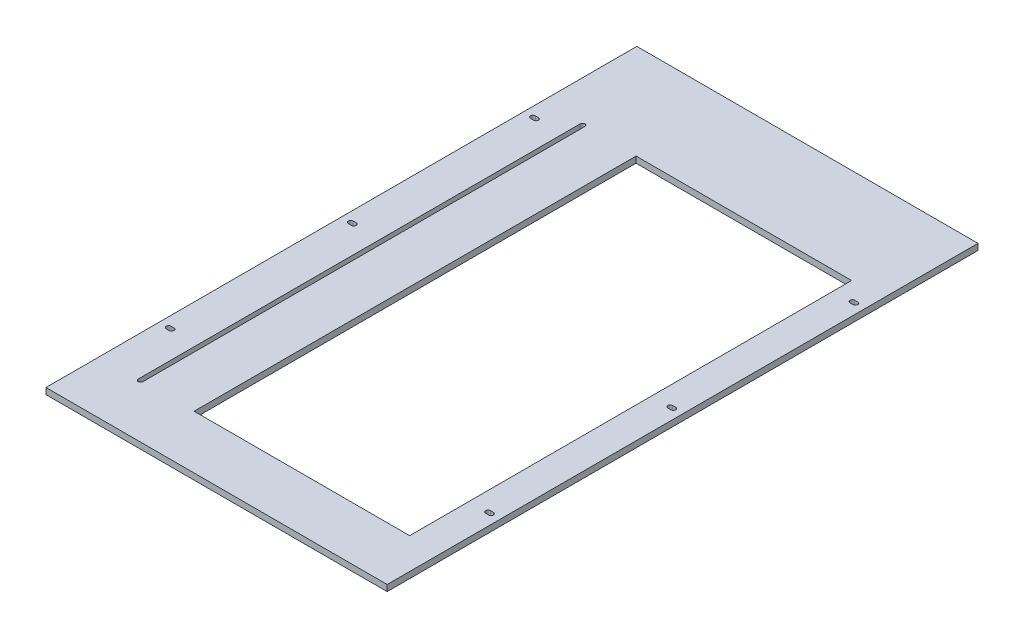
SolidWorks part; units mm, degrees
ref_plane "前基準面" through (0, 0, 0) normal (0, 0, 1) x (1, 0, 0)
ref_plane "上基準面" through (0, 0, 0) normal (0, 1, 0) x (1, 0, 0)
ref_plane "右基準面" through (0, 0, 0) normal (1, 0, 0) x (0, 0, -1)
sketch "草圖1" plane through (0, 0, 0) normal (0, 1, 0) x (1, 0, 0)
  line L0 (0, 0) -> (326.8973, 0) construction
  line L1 (0, 0) -> (0, 183.7767) construction
  line L3 (-113.7553, 194.0216) -> (106.2447, 194.0216)
  line L4 (-113.7553, 194.0216) -> (-113.7553, -186.9784)
  line L5 (-113.7553, -186.9784) -> (106.2447, -186.9784)
  line L6 (106.2447, 194.0216) -> (106.2447, -186.9784)
  dimension "D1" = 381
  dimension "D2" = 220
extrude "填料-伸長1" add sketch "草圖1" against normal blind 4
sketch "草圖2" plane through (0, 0, 0) normal (0, 1, 0) x (1, 0, 0)
  line L0 (-113.7553, 194.0216) -> (-113.7553, -186.9784) construction
  line L1 (-113.7553, -186.9784) -> (106.2447, -186.9784) construction
  line L2 (-106.7553, -113.9784) -> (99.2447, -113.9784) construction
  line L3 (-106.7553, -113.9784) -> (-106.7553, 3.5216) construction
  point P0 (-106.7553, -113.9784)
  point P6 (99.2447, -113.9784)
  point P8 (99.2447, 3.5216)
  point P9 (99.2447, 121.0216)
  point P10 (-106.7553, 3.5216)
  point P11 (-106.7553, 121.0216)
  dimension "D1" = 7
  dimension "D2" = 73
  dimension "D5" = 206
  dimension "D6" = 117.5
  dimension "D3" = 2
  dimension "D4" = 3
hole_wizard "Ø2.9 (2.9) 直徑孔1" positions "3D草圖4" profile "草圖5" hole size "Ø2.9" standard "GB" end condition through all
sketch3d "3D草圖4"
  point P0 (-106.7553, 0, -121.0216)
  point P3 (-106.7553, 0, -3.5216)
  point P6 (-106.7553, 0, 113.9784)
  point P9 (99.2447, 0, 113.9784)
  point P12 (99.2447, 0, -3.5216)
  point P15 (99.2447, 0, -121.0216)
sketch "草圖5" plane through (-106.7553, 0, -121.0216) normal (1, 0, 0) x (0, 0, 1)
  line L0 (0, 0) -> (0, 4)
  line L1 (0, 4) -> (1.45, 4)
  line L2 (1.45, 4) -> (1.45, 0)
  line L5 (1.45, 0) -> (0, 0)
  line L11 (0, -6.35) -> (0, 107.95) construction
  dimension "貫穿孔直徑" = 2.9
  dimension "貫穿孔深度" = 4
sketch "草圖6" plane through (0, 0, 0) normal (0, 1, 0) x (1, 0, 0)
  line L0 (-113.7553, -186.9784) -> (106.2447, -186.9784) construction
  line L1 (-52.7553, 132.5216) -> (86.2447, 132.5216)
  line L2 (-52.7553, 132.5216) -> (-52.7553, -152.4784)
  line L3 (-52.7553, -152.4784) -> (86.2447, -152.4784)
  line L4 (86.2447, 132.5216) -> (86.2447, -152.4784)
  line L5 (106.2447, -186.9784) -> (106.2447, 194.0216) construction
  dimension "D1" = 139
  dimension "D2" = 285
  dimension "D3" = 34.5
  dimension "D4" = 20
extrude "除料-伸長2" cut sketch "草圖6" against normal through all
sketch "草圖7" plane through (0, 0, 0) normal (0, 1, 0) x (1, 0, 0)
  line L0 (-107.7553, 121.0216) -> (-105.7553, 121.0216) construction
  line L1 (-107.7553, 122.5216) -> (-105.7553, 122.5216)
  line L2 (-107.7553, 119.5216) -> (-105.7553, 119.5216)
  line L3 (98.2447, 121.0216) -> (100.2447, 121.0216) construction
  line L4 (98.2447, 122.5216) -> (100.2447, 122.5216)
  line L5 (98.2447, 119.5216) -> (100.2447, 119.5216)
  line L6 (98.2447, 3.5216) -> (100.2447, 3.5216) construction
  line L7 (98.2447, 5.0216) -> (100.2447, 5.0216)
  line L8 (98.2447, 2.0216) -> (100.2447, 2.0216)
  line L9 (98.2447, -113.9784) -> (100.2447, -113.9784) construction
  line L10 (98.2447, -112.4784) -> (100.2447, -112.4784)
  line L11 (98.2447, -115.4784) -> (100.2447, -115.4784)
  line L12 (-107.7553, 3.5216) -> (-105.7553, 3.5216) construction
  line L13 (-107.7553, 5.0216) -> (-105.7553, 5.0216)
  line L14 (-107.7553, 2.0216) -> (-105.7553, 2.0216)
  line L15 (-107.7553, -113.9784) -> (-105.7553, -113.9784) construction
  line L16 (-107.7553, -112.4784) -> (-105.7553, -112.4784)
  line L17 (-107.7553, -115.4784) -> (-105.7553, -115.4784)
  line L18 (-107.7553, 121.0216) -> (98.2447, 121.0216) construction
  line L19 (-107.7553, 121.0216) -> (-107.7553, 3.5216) construction
  arc A0 (-107.7553, 122.5216) -> (-107.7553, 119.5216) centre (-107.7553, 121.0216) ccw
  arc A1 (-105.7553, 119.5216) -> (-105.7553, 122.5216) centre (-105.7553, 121.0216) ccw
  arc A2 (98.2447, 122.5216) -> (98.2447, 119.5216) centre (98.2447, 121.0216) ccw
  arc A3 (100.2447, 119.5216) -> (100.2447, 122.5216) centre (100.2447, 121.0216) ccw
  arc A4 (98.2447, 5.0216) -> (98.2447, 2.0216) centre (98.2447, 3.5216) ccw
  arc A5 (100.2447, 2.0216) -> (100.2447, 5.0216) centre (100.2447, 3.5216) ccw
  arc A6 (98.2447, -112.4784) -> (98.2447, -115.4784) centre (98.2447, -113.9784) ccw
  arc A7 (100.2447, -115.4784) -> (100.2447, -112.4784) centre (100.2447, -113.9784) ccw
  arc A8 (-107.7553, 5.0216) -> (-107.7553, 2.0216) centre (-107.7553, 3.5216) ccw
  arc A9 (-105.7553, 2.0216) -> (-105.7553, 5.0216) centre (-105.7553, 3.5216) ccw
  arc A10 (-107.7553, -112.4784) -> (-107.7553, -115.4784) centre (-107.7553, -113.9784) ccw
  arc A11 (-105.7553, -115.4784) -> (-105.7553, -112.4784) centre (-105.7553, -113.9784) ccw
  point P2 (-106.7553, 121.0216)
  point P13 (99.2447, 121.0216)
  point P20 (99.2447, 3.5216)
  point P27 (99.2447, -113.9784)
  point P34 (-106.7553, 3.5216)
  point P41 (-106.7553, -113.9784)
  circle M11 centre (-106.7553, 3.5216) radius 1.45
  circle M13 centre (99.2447, -113.9784) radius 1.45
  circle M14 centre (99.2447, 3.5216) radius 1.45
  circle M15 centre (99.2447, 121.0216) radius 1.45
  dimension "D2" = 1.5
  dimension "D1" = 2
  dimension "D5" = 206
  dimension "D6" = 117.5
  dimension "D3" = 2
  dimension "D4" = 3
extrude "除料-伸長3" cut sketch "草圖7" against normal through all contours L5 A3 L4 A2 M15 | L14 A9 L13 A8 M11 | L8 A5 L7 A4 M14 | L11 A7 L10 A6 M13 | L2 A1 L1 A0 | A11 L16 A10 L17 region at (99.2447, 0, -122.5158) region at (99.2447, 0, -5.0158) region at (99.2447, 0, 112.4842) region at (-106.7553, 0, -5.0158)
sketch "草圖8" plane through (0, 0, 0) normal (0, 1, 0) x (1, 0, 0)
  line L0 (-87.2553, 132.5216) -> (-87.2553, -152.4784) construction
  line L1 (86.2447, 132.5216) -> (-52.7553, 132.5216) construction
  line L2 (-52.7553, -152.4784) -> (86.2447, -152.4784) construction
  line L4 (-87.2553, 132.5216) -> (-87.2553, -152.4784) construction
  line L5 (-85.7553, 132.5216) -> (-85.7553, -152.4784)
  line L6 (-88.7553, 132.5216) -> (-88.7553, -152.4784)
  line L7 (-113.7553, 194.0216) -> (-113.7553, -186.9784) construction
  arc A0 (-85.7553, 132.5216) -> (-88.7553, 132.5216) centre (-87.2553, 132.5216) ccw
  arc A1 (-88.7553, -152.4784) -> (-85.7553, -152.4784) centre (-87.2553, -152.4784) ccw
  point P2 (-87.2553, -9.9784)
  dimension "D2" = 1.5
  dimension "D1" = 25
extrude "除料-伸長4" cut sketch "草圖8" against normal through all
